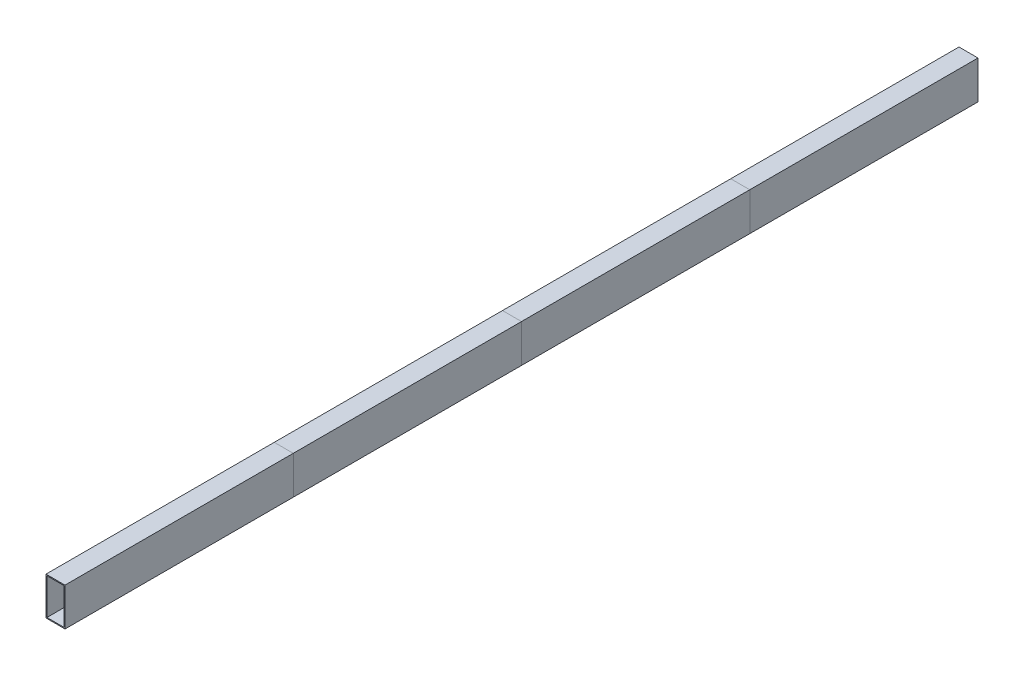
SolidWorks part; units mm, degrees
ref_plane "Спереди" through (0, 0, 0) normal (0, 0, 1) x (1, 0, 0)
ref_plane "Сверху" through (0, 0, 0) normal (0, 1, 0) x (1, 0, 0)
ref_plane "Справа" through (0, 0, 0) normal (1, 0, 0) x (0, 0, -1)
sketch "Эскиз1" plane through (0, 0, 0) normal (0, 0, 1) x (1, 0, 0)
  line L1 (-50, -100) -> (50, -100)
  line L2 (-50, -100) -> (-50, 100)
  line L3 (-50, 100) -> (50, 100)
  line L4 (50, -100) -> (50, 100)
  line L5 (-50, -100) -> (50, 100) construction
  line L6 (-50, 100) -> (50, -100) construction
  line L7 (-45, -95) -> (45, -95)
  line L8 (-45, -95) -> (-45, 95)
  line L9 (-45, 95) -> (45, 95)
  line L10 (45, -95) -> (45, 95)
  line L11 (-45, -95) -> (45, 95) construction
  line L12 (-45, 95) -> (45, -95) construction
  point P0 (0, 0)
  point P6 (0, 0)
  dimension "D1" = 100
  dimension "D2" = 200
  dimension "D3" = 90
  dimension "D4" = 190
extrude "Бобышка-Вытянуть1" add sketch "Эскиз1" along normal blind 1200
extrude "Бобышка-Вытянуть2" add sketch "Эскиз1<2>" along normal blind 1200 from surface separate body starting at face at (0, 0, 1200)
sketch "Эскиз1<2>" plane through (0, 0, 0) normal (0, 0, 1) x (1, 0, 0) same geometry as "Эскиз1"
extrude "Бобышка-Вытянуть3" add sketch "Эскиз1<3>" along normal blind 1200 from surface separate body starting at face at (0, 0, 2400)
sketch "Эскиз1<3>" plane through (0, 0, 0) normal (0, 0, 1) x (1, 0, 0) same geometry as "Эскиз1"
extrude "Бобышка-Вытянуть4" add sketch "Эскиз1<4>" along normal blind 1200 from surface separate body starting at face at (0, 0, 3600)
sketch "Эскиз1<4>" plane through (0, 0, 0) normal (0, 0, 1) x (1, 0, 0) same geometry as "Эскиз1"
ref_point "Точка1"
ref_point "Точка2"
